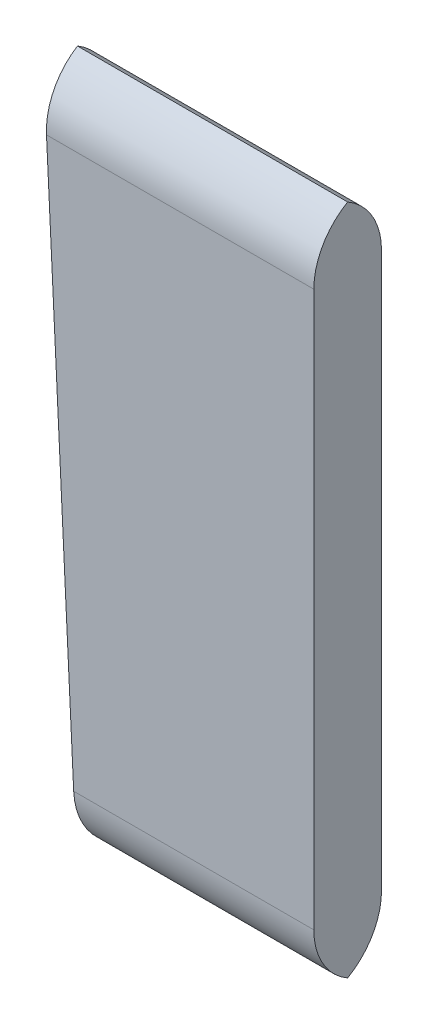
SolidWorks part; units mm, degrees
ref_plane "Front Plane" through (0, 0, 0) normal (0, 0, 1) x (1, 0, 0)
ref_plane "Top Plane" through (0, 0, 0) normal (0, 1, 0) x (1, 0, 0)
ref_plane "Right Plane" through (0, 0, 0) normal (1, 0, 0) x (0, 0, -1)
sketch "Sketch2" plane through (0, 0, 0) normal (0, 0, 1) x (1, 0, 0)
  line L0 (-10.989, 64.1978) -> (29.011, 64.1978)
  line L1 (29.011, 64.1978) -> (29.011, -37.8022)
  line L2 (29.011, -37.8022) -> (-5.989, -37.8022)
  line L3 (-5.989, -37.8022) -> (-10.989, 64.1978)
  point P6 (-182.1978, 56.7033)
extrude "Boss-Extrude1" add sketch "Sketch2" along normal blind 10
fillet "Fillet1" radius 10 2 edges at (9.011, 64.1978, 0) (9.011, 64.1978, 10)
fillet "Fillet2" radius 10 2 edges at (11.511, -37.8022, 0) (11.511, -37.8022, 10)
